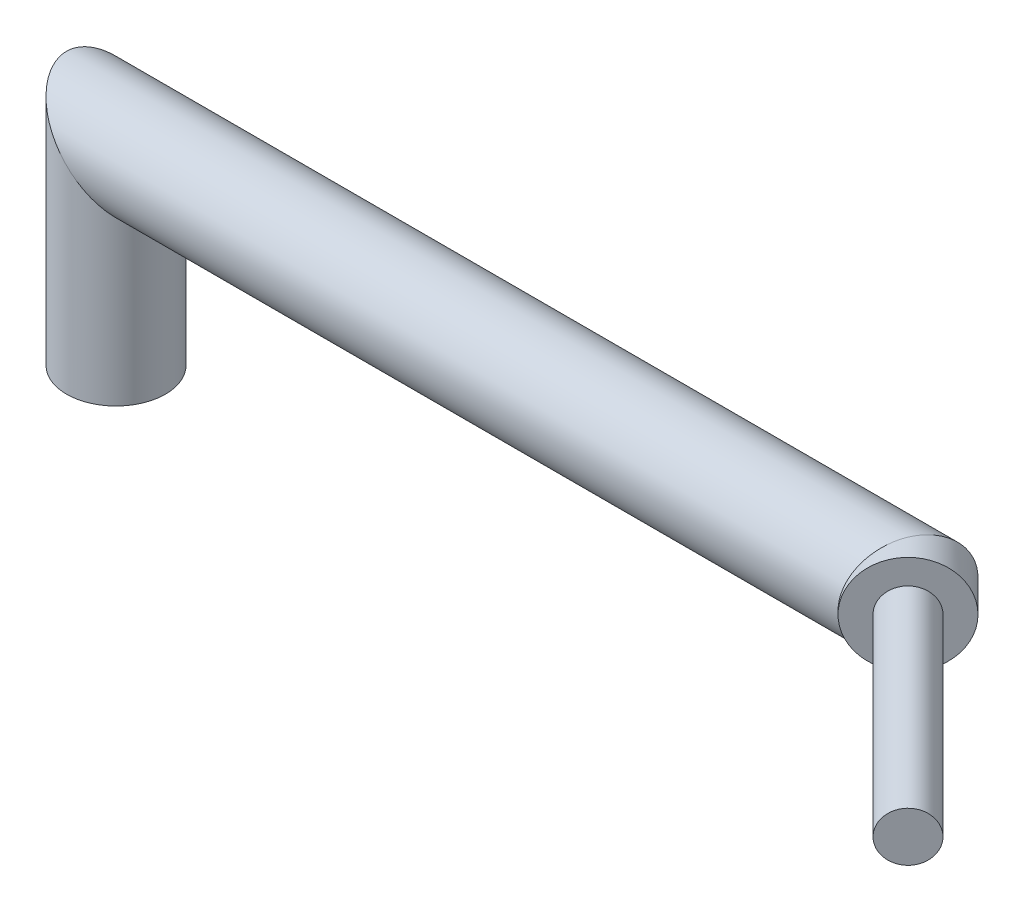
SolidWorks part; units mm, degrees
ref_plane "Front Plane" through (0, 0, 0) normal (0, 0, 1) x (1, 0, 0)
ref_plane "Top Plane" through (0, 0, 0) normal (0, 1, 0) x (1, 0, 0)
ref_plane "Right Plane" through (0, 0, 0) normal (1, 0, 0) x (0, 0, -1)
sketch3d "3DSketch2"
  line L0 (0, 0, 0) -> (0, 40, 0)
  line L1 (0, 40, 0) -> (160, 40, 0)
  line L2 (160, 40, 0) -> (202.4264, 40, -42.4264)
  dimension "D1" = 40
  dimension "D2" = 160
  dimension "D3" = 135
  dimension "D4" = 60
sweep "Sweep1" add path "3DSketch2" circular profile diameter 20 parameters "D3"=20
mirror "Mirror2" about plane through (0, 0, 0) normal (0, 0, 1) of bodies 101
delete or keep bodies "Body-Delete/Keep 1" type delete bodies bodies 101
sketch "Sketch2" plane through (122.4264, 0, 122.4264) normal (0.7071, 0, 0.7071) x (0.7071, 0, -0.7071)
  circle A0 centre (113.1371, 40) radius 5
  circle M1 centre (113.1371, 40) radius 10
  dimension "D1" = 10
extrude "Cut-Extrude1" cut sketch "Sketch2" against normal blind 55 contours A0 M1 region at (195.5553, 40, 49.2975)
shell "Shell1" thickness 2 removed face at (0, 0, -10)
